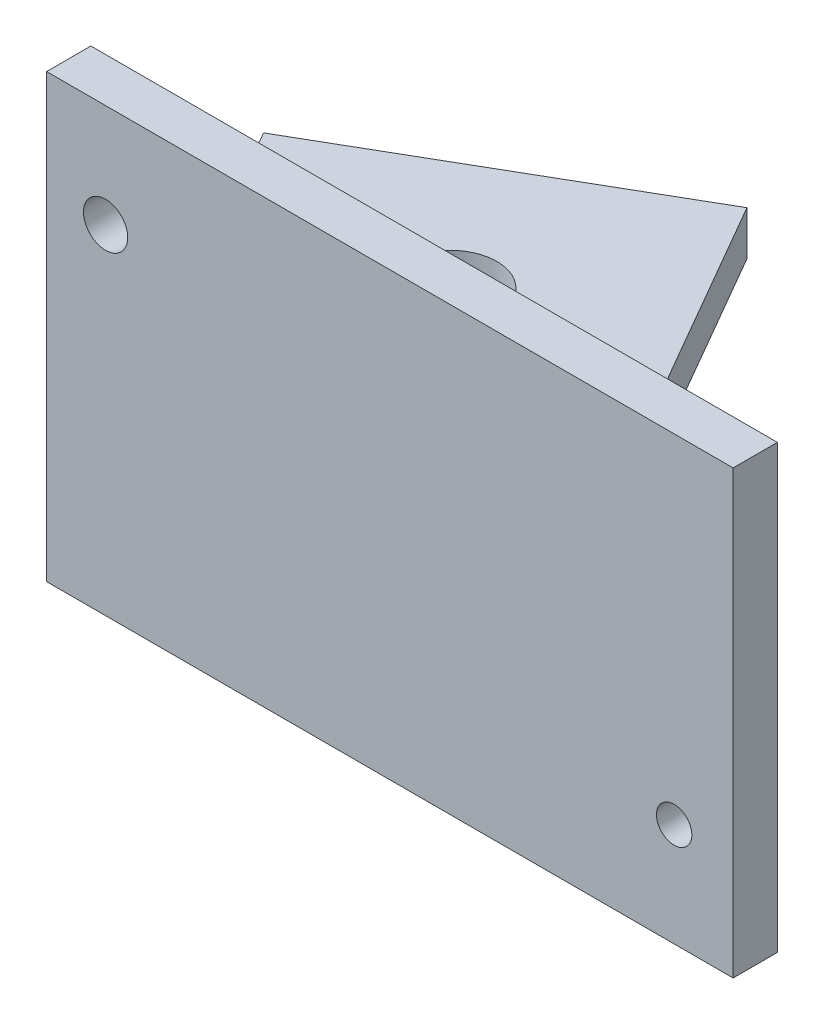
SolidWorks part; units mm, degrees
ref_plane "Front Plane" through (0, 0, 0) normal (0, 0, 1) x (1, 0, 0)
ref_plane "Top Plane" through (0, 0, 0) normal (0, 1, 0) x (1, 0, 0)
ref_plane "Right Plane" through (0, 0, 0) normal (1, 0, 0) x (0, 0, -1)
sketch "Sketch1" plane through (0, 0, 0) normal (0, 0, 1) x (1, 0, 0)
  line L1 (0, 0) -> (33.782, 0) construction
  line L2 (0, 0) -> (0, 19.812) construction
  line L3 (0, 19.812) -> (33.782, 19.812) construction
  line L4 (33.782, 0) -> (33.782, 19.812) construction
  line L5 (-1.5875, -1.5875) -> (35.3695, -1.5875)
  line L6 (-1.5875, -1.5875) -> (-1.5875, 19.812)
  line L7 (-1.5875, 19.812) -> (35.3695, 19.812)
  line L8 (35.3695, -1.5875) -> (35.3695, 19.812)
  circle A0 centre (1.5875, 14.2558) radius 1.1906
  circle A1 centre (32.1945, 1.5875) radius 0.9525
  dimension "D3" = 2.3813
  dimension "D4" = 1.905
  dimension "D5" = 1.5875
  dimension "D6" = 1.5875
  dimension "D7" = 1.5875
  dimension "D8" = 5.5562
  dimension "D9" = 3.175
  dimension "D11" = 3.175
  dimension "D12" = 5.5562
  dimension "D1" = 19.812
  dimension "D2" = 33.782
  dimension "D10" = 3.175
extrude "Boss-Extrude1" add sketch "Sketch1" along normal blind 2.3813
sketch "Sketch2" plane through (0, -1.5875, 0) normal (0, -1, 0) x (1, 0, 0)
  line L8 (-1.5875, 0) -> (20.4095, 0) construction
  line L9 (-1.5875, 2.3813) -> (35.3695, 2.3813)
  line L10 (-1.5875, 2.3813) -> (-1.5875, 0)
  line L12 (35.3695, 2.3813) -> (35.3695, 0)
  line L15 (2.2103, -31.522) -> (-14.2875, -21.997)
  line L16 (-1.5875, 0) -> (-14.2875, -21.997)
  line L17 (2.2103, -31.522) -> (20.4095, 0)
  line L18 (20.4095, 0) -> (35.3695, 0)
  dimension "D1" = 19.05
  dimension "D2" = 60
  dimension "D3" = 25.4
extrude "Boss-Extrude3" add sketch "Sketch2" along normal blind 2.3813
sketch "Sketch4" plane through (0, -1.5875, 0) normal (0, 1, 0) x (1, 0, 0)
  line L0 (-6.0386, 26.7595) -> (-2.019, 19.7973) construction
  line L1 (-14.2875, 21.997) -> (2.2103, 31.522) construction
  line L2 (-2.019, 19.7973) -> (4.331, 8.7988) construction
  line L3 (4.331, 8.7988) -> (9.411, 0) construction
  line L4 (-1.5875, 0) -> (20.4095, 0) construction
  circle A0 centre (-2.019, 19.7973) radius 2.4892
  circle A1 centre (4.331, 8.7988) radius 2.4892
  dimension "D1" = 4.9784
  dimension "D2" = 12.7
  dimension "D3" = 10.16
extrude "Cut-Extrude2" cut sketch "Sketch4" against normal up to next
